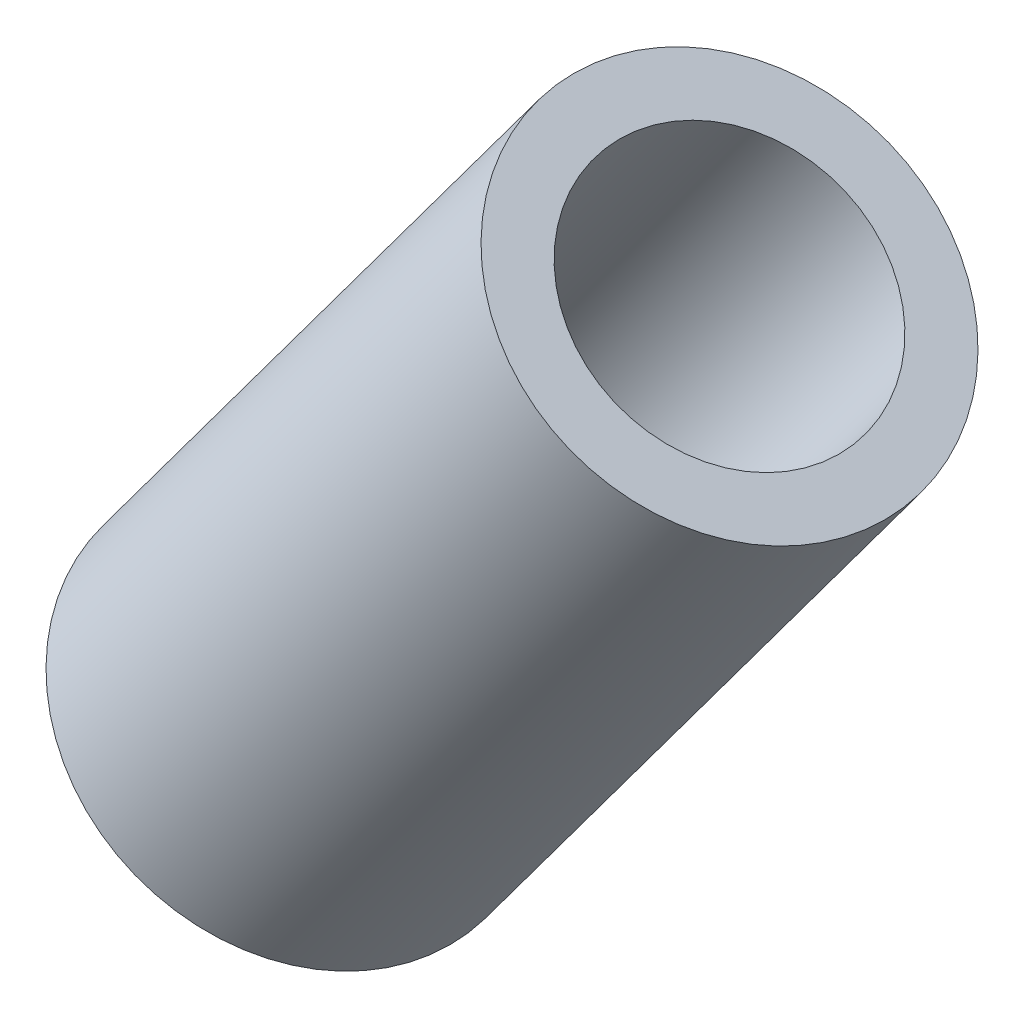
SolidWorks part; units mm, degrees
material "Silicon Rubber"
ref_plane "X-Y Datum" through (0, 0, 0) normal (0, 0, 1) x (1, 0, 0)
ref_plane "X-Z Datum" through (0, 0, 0) normal (0, 1, 0) x (1, 0, 0)
ref_plane "Y-Z Datum" through (0, 0, 0) normal (1, 0, 0) x (0, 0, -1)
sketch3d "3DSketch1"
  line L0 (0, 0, 0) -> (30.2901, 40.7817, 0)
  dimension "D1" = 50.8
sweep "Sweep1" add path "3DSketch1" circular profile diameter 26.9875 parameters "D3"=26.9875
sweep "Cut-Sweep1" cut path "3DSketch1<2>" circular profile diameter 19.05 parameters "D3"=19.05
sketch3d "3DSketch1<2>" same geometry as "3DSketch1"
sketch3d "3DSketch2"
  line L0 (0, 0, 0) -> (30.2901, 40.7817, 0) construction
  circle A1 centre (15.1451, 20.3909, 0) radius 9.525 construction
  circle A4 centre (30.2901, 40.7817, 0) radius 9.525 construction
  point P4 (9.4657, 12.7443, 0)
  point P8 (24.6107, 33.1351, 0)
